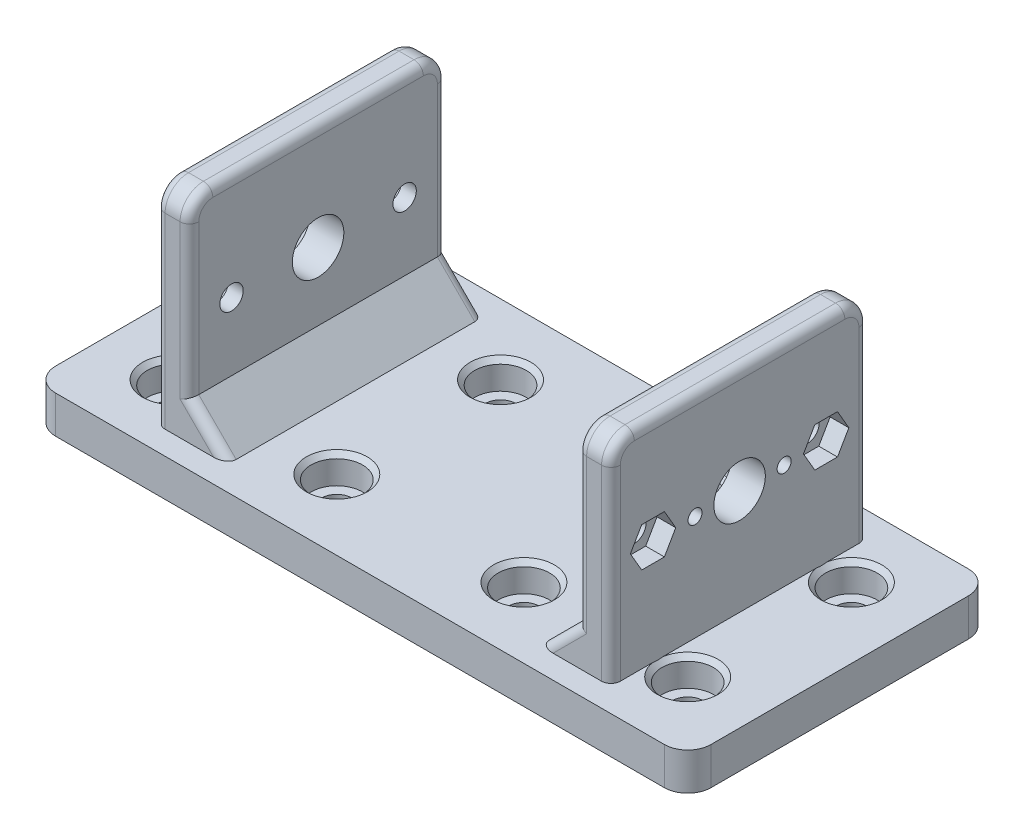
SolidWorks part; units mm, degrees
ref_plane "Front Plane" through (0, 0, 0) normal (0, 0, 1) x (1, 0, 0)
ref_plane "Top Plane" through (0, 0, 0) normal (0, 1, 0) x (1, 0, 0)
ref_plane "Right Plane" through (0, 0, 0) normal (1, 0, 0) x (0, 0, -1)
sketch "Sketch1" plane through (0, 0, 0) normal (0, 1, 0) x (1, 0, 0)
  line L0 (0, 14.013) -> (0, -13.1268) construction
  line L1 (-3.8771, 0) -> (4.5418, 0) construction
  line L2 (-37.5, 17.5) -> (-37.5, -17.5) construction
  line L3 (70, 32.5) -> (-70, 32.5)
  line L4 (-70, 32.5) -> (-70, -32.5)
  line L5 (70, -32.5) -> (-70, -32.5)
  line L6 (70, 32.5) -> (70, -32.5)
  circle A0 centre (-37.5, 0) radius 10 construction
  circle A1 centre (-55, 17.5) radius 3.25
  circle A2 centre (-55, -17.5) radius 3.25
  circle A3 centre (-20, -17.5) radius 3.25
  circle A4 centre (-20, 17.5) radius 3.25
  circle A5 centre (55, -17.5) radius 3.25
  circle A6 centre (20, -17.5) radius 3.25
  circle A7 centre (20, 17.5) radius 3.25
  circle A8 centre (37.5, 0) radius 10 construction
  circle A9 centre (55, 17.5) radius 3.25
  circle A10 centre (-55, 17.5) radius 5.5 construction
  circle A11 centre (-20, 17.5) radius 5.5 construction
  circle A12 centre (-20, -17.5) radius 5.5 construction
  circle A13 centre (-55, -17.5) radius 5.5 construction
  circle A14 centre (20, -17.5) radius 5.5 construction
  circle A15 centre (20, 17.5) radius 5.5 construction
  circle A16 centre (55, 17.5) radius 5.5 construction
  circle A17 centre (55, -17.5) radius 5.5 construction
  point P19 (-70, 0)
  point P33 (0, -32.5)
  point P34 (0, 32.5)
  dimension "D1" = 20
  dimension "D2" = 6.5
  dimension "D10" = 11
  dimension "D3" = 35
  dimension "D4" = 35
  dimension "D5" = 75
  dimension "D6" = 15
  dimension "D7" = 15
  dimension "D8" = 65
  dimension "D9" = 140
extrude "Boss-Extrude1" add sketch "Sketch1" along normal blind 8
sketch "Sketch5" plane through (0, 8, 0) normal (0, 1, 0) x (1, 0, 0)
  circle A0 centre (-55, 17.5) radius 5.5
  circle A1 centre (-20, 17.5) radius 5.5
  circle A2 centre (20, 17.5) radius 5.5
  circle A3 centre (55, 17.5) radius 5.5
  circle A4 centre (55, -17.5) radius 5.5
  circle A5 centre (20, -17.5) radius 5.5
  circle A6 centre (-20, -17.5) radius 5.5
  circle A7 centre (-55, -17.5) radius 5.5
  dimension "D1" = 11
extrude "Cut-Extrude1" cut sketch "Sketch5" against normal blind 6
sketch "Sketch3" plane through (-70, 0, 0) normal (-1, 0, 0) x (0, 0, 1)
  line L0 (-32.5, 0) -> (-32.5, 8)
  line L1 (-32.5, 8) -> (32.5, 8) construction
  line L2 (-32.5, 8) -> (32.5, 8)
  line L3 (32.5, 8) -> (32.5, 0)
  line L4 (32.5, 0) -> (-32.5, 0)
extrude "Boss-Extrude3" add sketch "Sketch3" along normal blind 0.1
sketch "Sketch4" plane through (0, 8, 0) normal (0, 1, 0) x (1, 0, 0)
  line L0 (-48.7, 27.5) -> (-48.7, -27.5)
  line L1 (-48.7, -27.5) -> (-41.5, -27.5)
  line L2 (70, -32.5) -> (70, 32.5) construction
  line L3 (-41.5, -27.5) -> (-41.5, 27.5)
  line L5 (-41.5, 27.5) -> (-48.7, 27.5)
  line L12 (48.6, 27.5) -> (41.4, 27.5)
  line L13 (41.4, 27.5) -> (41.4, -27.5)
  line L14 (41.4, -27.5) -> (48.6, -27.5)
  line L15 (48.6, 27.5) -> (48.6, -27.5)
  line L16 (-70.1, -32.5) -> (-70.1, 32.5) construction
  line L17 (0, 0) -> (-70.1, 0) construction
  point P4 (0, 0)
  point P6 (43.6, 20.9205)
  point P7 (43.4062, 24.4715)
  point P9 (45, 27.5)
  point P12 (0, 0)
  point P19 (0, 0)
  point P20 (0, 0)
  point P21 (0, 0)
  point P22 (-45.1, 27.5)
  point P25 (0, 0)
  dimension "D1" = 7.2
  dimension "D2" = 25
  dimension "D3" = 55
  dimension "D4" = 25
  dimension "D5" = 55
  dimension "D6" = 7.2
extrude "Boss-Extrude4" add sketch "Sketch4" along normal blind 45
sketch "Sketch6" plane through (-70.1, 0, 0) normal (-1, 0, 0) x (0, 0, 1)
  line L0 (-32.5, 8) -> (32.5, 8) construction
  line L1 (-32.5, 8) -> (-32.5, 0) construction
  line L2 (32.5, 0) -> (32.5, 8) construction
  line L3 (-32.5, 0) -> (32.5, 0) construction
  line L4 (0, 53) -> (0, 8) construction
  line L5 (-27.5, 53) -> (27.5, 53) construction
  line L6 (0, 30.5) -> (-32.5, 30.5) construction
  line L7 (0, 30.5) -> (32.5, 30.5) construction
  circle A0 centre (0, 30.5) radius 5.5
  circle A1 centre (-18.5, 30.5) radius 2.5
  circle A2 centre (18.5, 30.5) radius 2.5
  dimension "D2" = 11
  dimension "D3" = 5
  dimension "D1" = 8
  dimension "D4" = 37
extrude "Cut-Extrude2" cut sketch "Sketch6" against normal through all both and the other way through all
sketch "Sketch8" plane through (48.6, 0, 0) normal (1, 0, 0) x (0, 0, -1)
  line L0 (-9.525, 30.5) -> (9.525, 30.5) construction
  circle A0 centre (0, 30.5) radius 9.525 construction
  circle A1 centre (9.525, 30.5) radius 1.5
  circle A2 centre (-9.525, 30.5) radius 1.5
  dimension "D1" = 19.05
  dimension "D2" = 3
extrude "Cut-Extrude3" cut sketch "Sketch8" against normal blind 10
sketch "Sketch9" plane through (48.6, 0, 0) normal (1, 0, 0) x (0, 0, -1)
  line L0 (-27.5, 8) -> (27.5, 8) construction
  line L1 (23.3497, 30.5) -> (20.9249, 34.7)
  line L2 (20.9249, 34.7) -> (16.0751, 34.7)
  line L3 (16.0751, 34.7) -> (13.6503, 30.5)
  line L4 (13.6503, 30.5) -> (16.0751, 26.3)
  line L5 (16.0751, 26.3) -> (20.9249, 26.3)
  line L6 (20.9249, 26.3) -> (23.3497, 30.5)
  line L7 (-13.6503, 30.5) -> (-16.0751, 34.7)
  line L8 (-16.0751, 34.7) -> (-20.9249, 34.7)
  line L9 (-20.9249, 34.7) -> (-23.3497, 30.5)
  line L10 (-23.3497, 30.5) -> (-20.9249, 26.3)
  line L11 (-20.9249, 26.3) -> (-16.0751, 26.3)
  line L12 (-16.0751, 26.3) -> (-13.6503, 30.5)
  circle A0 centre (18.5, 30.5) radius 4.2 construction
  circle A1 centre (-18.5, 30.5) radius 4.2 construction
  dimension "D1" = 8.4
  dimension "D2" = 8.4
extrude "Cut-Extrude4" cut sketch "Sketch9" against normal blind 4
sketch "Sketch11" plane through (41.4, 0, 0) normal (-1, 0, 0) x (0, 0, 1)
  line L1 (12.525, 32.2321) -> (9.525, 33.9641)
  line L2 (9.525, 33.9641) -> (6.525, 32.2321)
  line L3 (6.525, 32.2321) -> (6.525, 28.7679)
  line L4 (6.525, 28.7679) -> (9.525, 27.0359)
  line L5 (9.525, 27.0359) -> (12.525, 28.7679)
  line L6 (12.525, 28.7679) -> (12.525, 32.2321)
  line L7 (-9.525, 33.9641) -> (-12.525, 32.2321)
  line L8 (-12.525, 32.2321) -> (-12.525, 28.7679)
  line L9 (-12.525, 28.7679) -> (-9.525, 27.0359)
  line L10 (-9.525, 27.0359) -> (-6.525, 28.7679)
  line L11 (-6.525, 28.7679) -> (-6.525, 32.2321)
  line L12 (-6.525, 32.2321) -> (-9.525, 33.9641)
  circle A0 centre (9.525, 30.5) radius 3 construction
  circle A1 centre (-9.525, 30.5) radius 3 construction
  point P10 (-6.525, 30.5)
  dimension "D1" = 6
  dimension "D2" = 6
extrude "Cut-Extrude6" cut sketch "Sketch11" against normal blind 3.5
sketch "Sketch12" plane through (-48.7, 0, 0) normal (-1, 0, 0) x (0, 0, 1)
  line L1 (-14.3, 32.9249) -> (-18.5, 35.3497)
  line L2 (-18.5, 35.3497) -> (-22.7, 32.9249)
  line L3 (-22.7, 32.9249) -> (-22.7, 28.0751)
  line L4 (-22.7, 28.0751) -> (-18.5, 25.6503)
  line L5 (-18.5, 25.6503) -> (-14.3, 28.0751)
  line L6 (-14.3, 28.0751) -> (-14.3, 32.9249)
  line L7 (22.7, 32.9249) -> (18.5, 35.3497)
  line L8 (18.5, 35.3497) -> (14.3, 32.9249)
  line L9 (14.3, 32.9249) -> (14.3, 28.0751)
  line L10 (14.3, 28.0751) -> (18.5, 25.6503)
  line L11 (18.5, 25.6503) -> (22.7, 28.0751)
  line L12 (22.7, 28.0751) -> (22.7, 32.9249)
  circle A0 centre (-18.5, 30.5) radius 4.2 construction
  circle A1 centre (18.5, 30.5) radius 4.2 construction
  dimension "D1" = 8.4
  dimension "D2" = 8.4
extrude "Cut-Extrude7" cut sketch "Sketch12" against normal blind 4
chamfer "Chamfer2" distance 1 angle 45 8 edges at (55, 8, -12) (55, 8, 23) (-55, 8, -12) (-55, 8, 23) (-20, 8, 23) (-20, 8, -12) (20, 8, -12) (20, 8, 23)
chamfer "Chamfer3" distance 8 angle 45 2 edges at (41.4, 8, 0) (-41.5, 8, 0)
fillet "Fillet6" radius 5 8 edges at (-45.1, 53, -27.5) (45, 53, -27.5) (45, 53, 27.5) (-45.1, 53, 27.5) (70, 4, -32.5) (70, 4, 32.5) (-70.1, 4, -32.5) (-70.1, 4, 32.5)
fillet "Fillet7" radius 2 24 edges at (48.6, 28, -27.5) (48.6, 51.5355, -26.0355) (48.6, 53, 0) (48.6, 51.5355, 26.0355) (41.4, 32, -27.5) (41.4, 51.5355, -26.0355) (41.4, 53, 0) (41.4, 51.5355, 26.0355) (-41.5, 32, -27.5) (-41.5, 51.5355, -26.0355) (-41.5, 53, 0) (-41.5, 51.5355, 26.0355) (-48.7, 28, -27.5) (-48.7, 51.5355, -26.0355) (-48.7, 53, 0) (-48.7, 51.5355, 26.0355) (37.4, 12, 27.5) (37.4, 12, -27.5) (-37.5, 12, -27.5) (-37.5, 12, 27.5) (48.6, 28, 27.5) (41.4, 32, 27.5) (-41.5, 32, 27.5) (-48.7, 28, 27.5)
